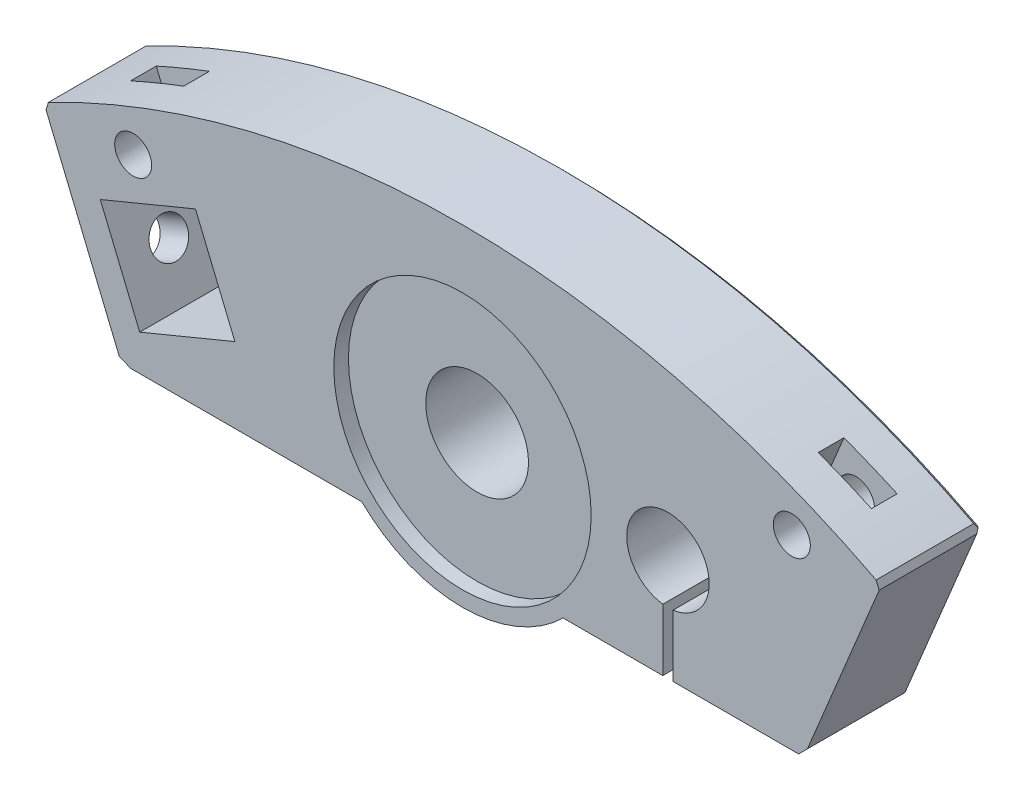
SolidWorks part; units mm, degrees
ref_plane "Front Plane" through (0, 0, 0) normal (0, 0, 1) x (1, 0, 0)
ref_plane "Top Plane" through (0, 0, 0) normal (0, 1, 0) x (1, 0, 0)
ref_plane "Right Plane" through (0, 0, 0) normal (1, 0, 0) x (0, 0, -1)
sketch "Sketch1" plane through (0, 0, 0) normal (0, 0, 1) x (1, 0, 0)
  line L0 (-46.9014, 0) -> (43.5211, 0) construction
  line L1 (0, 38.5211) -> (0, -80.4339) construction
  line L2 (-33.5349, -69.25) -> (36.7559, -69.25) construction
  line L3 (0, -69.25) -> (-37.9703, 22.4183) construction
  line L4 (-40.7467, 8.1836) -> (-33.2148, -10)
  line L5 (-25.9885, 6.5901) -> (-35.2504, 2.7537)
  line L6 (-35.2504, 2.7537) -> (-31.414, -6.5082)
  line L7 (-31.414, -6.5082) -> (-22.1521, -2.6718)
  line L8 (-22.1521, -2.6718) -> (-25.9885, 6.5901)
  line L9 (-33.2148, -10) -> (-9.798, -10)
  line L10 (33.2148, -10) -> (20.5, -10)
  line L11 (40.7467, 8.1836) -> (33.2148, -10)
  line L12 (20, 7.6703) -> (20, -11.9024) construction
  line L13 (19.5, -3.9812) -> (19.5, -10)
  line L14 (20.5, -3.9812) -> (20.5, -10)
  line L15 (19.5, -10) -> (9.798, -10)
  arc A0 (20.5, -3.9812) -> (19.5, -3.9812) centre (20, 0) ccw
  circle A1 centre (-28.7013, 0.041) radius 5.0125 construction
  arc A2 (40.7467, 8.1836) -> (-40.7467, 8.1836) centre (0, -69.25) ccw
  arc A5 (-9.798, -10) -> (9.798, -10) centre (0, 0) ccw
  circle A6 centre (0, 0) radius 5
  circle A7 centre (-32.0522, 8.1309) radius 1.8
  circle A8 centre (32.0522, 8.1309) radius 1.8
  dimension "D1" = 20
  dimension "D2" = 8.025
  dimension "D7" = 75
  dimension "D8" = 175
  dimension "D9" = 3
  dimension "D10" = 14
  dimension "D12" = 10
  dimension "D13" = 3.6
  dimension "D3" = 69.25
  dimension "D4" = 22.5
  dimension "D5" = 10.025
  dimension "D6" = 90
  dimension "D11" = 10
  dimension "D14" = 0.5
extrude "Boss-Extrude1" add sketch "Sketch1" along normal blind 10
sketch "Sketch2" plane through (0, 0, 10) normal (0, 0, 1) x (1, 0, 0)
  circle A0 centre (0, 0) radius 12.525
  dimension "D1" = 25.05
extrude "Cut-Extrude1" cut sketch "Sketch2" against normal blind 1.425
chamfer "Chamfer1" distance 0.5 5 edges at (-33.3322, -1.8772, 0) (-26.7831, -4.59, 0) (-24.0703, 1.9592, 0) (-30.6195, 4.6719, 0) (20, 4.0125, 0)
ref_plane "Plane1" through (0, 0, 3.75) normal (0, 0, 1) x (1, 0, 0)
sketch "Sketch3" plane through (0, 0, 3.75) normal (0, 0, 1) x (1, 0, 0)
  line L0 (-56.5816, 0) -> (49.5436, 0) construction
  line L1 (0, 34.2126) -> (0, -24.5915) construction
  line L2 (-26.7831, -4.59) -> (-35.1783, 15.678) construction
  line L3 (-31.414, -6.5082) -> (-22.1521, -2.6718) construction
  line L4 (-37.0768, 12.9445) -> (-33.5676, 4.4725)
  line L5 (-33.5676, 4.4725) -> (-28.3938, 6.6155)
  line L6 (-31.903, 15.0875) -> (-28.3938, 6.6155)
  line L7 (-37.0768, 12.9445) -> (-31.903, 15.0875)
  line L8 (37.0768, 12.9445) -> (33.5676, 4.4725)
  line L9 (33.5676, 4.4725) -> (28.3938, 6.6155)
  line L10 (31.903, 15.0875) -> (28.3938, 6.6155)
  line L11 (37.0768, 12.9445) -> (31.903, 15.0875)
  circle A0 centre (-32.0522, 8.1309) radius 1.8 construction
  point P15 (-30.9807, 5.544)
  dimension "D1" = 22.5
  dimension "D3" = 2.8
  dimension "D4" = 2.8
extrude "Cut-Extrude2" cut sketch "Sketch3" along normal blind 2.5
chamfer "Chamfer2" distance 0.5 angle 45 7 edges at (14.649, -10, 0) (0, -14, 0) (-21.5064, -10, 0) (-36.9808, -0.9082, 0) (26.8574, -10, 0) (36.9808, -0.9082, 0) (0, 18.25, 0)
sketch "Sketch4" plane through (-29.1145, -12.0596, 0) normal (0.9239, 0.3827, 0) x (0, 0, -1)
  line L0 (-11.0407, 11.0213) -> (-0.5, 11.0213) construction
  line L1 (-0.5, 6.0088) -> (-0.5, 16.0338) construction
  line L2 (-5.25, 6.0088) -> (-5.25, 12.0172) construction
  line L3 (-10, 6.0088) -> (-0.5, 6.0088) construction
  circle A0 centre (-5.25, 11.0213) radius 1.8
  dimension "D1" = 3.6
extrude "Cut-Extrude3" cut sketch "Sketch4" against normal blind 10
chamfer "Chamfer3" distance 0.5 angle 45 4 edges at (40.7467, 8.1836, 5.25) (33.2148, -10, 5.25) (-33.2148, -10, 5.25) (-40.7467, 8.1836, 5.25) first distance on face at (36.9808, -0.9082, 5.25) first distance on face at (26.8574, -10, 5.25) first distance on face at (-36.7927, -1.3623, 5.25) first distance on face at (0, 13.2168, 5.25)
